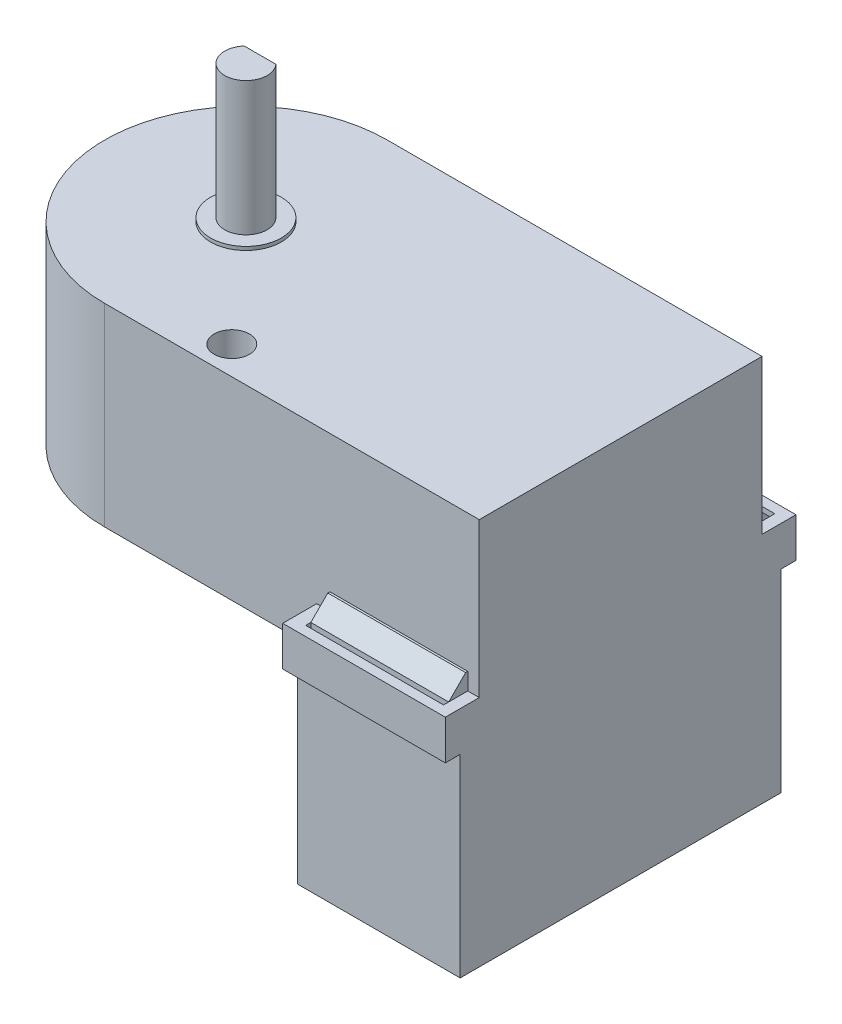
SolidWorks part; units mm, degrees
ref_plane "Спереди" through (0, 0, 0) normal (0, 0, 1) x (1, 0, 0)
ref_plane "Сверху" through (0, 0, 0) normal (0, 1, 0) x (1, 0, 0)
ref_plane "Справа" through (0, 0, 0) normal (1, 0, 0) x (0, 0, -1)
sketch "Эскиз1" plane through (0, 0, 0) normal (0, 1, 0) x (1, 0, 0)
  line L1 (-13.25, 10) -> (13.25, 10)
  line L3 (-13.25, -10) -> (13.25, -10)
  line L4 (13.25, 10) -> (13.25, -10)
  arc A0 (-13.25, -10) -> (-13.25, 10) centre (-13.25, 0) cw
extrude "Вытянуть1" add sketch "Эскиз1" along normal blind 13.7
sketch "Эскиз2" plane through (0, 13.7, 0) normal (0, 1, 0) x (1, 0, 0)
  line L0 (-13.25, 0) -> (-6.946, 0) construction
  line L1 (-14.368, 1) -> (-12.132, 1)
  arc A0 (-14.368, 1) -> (-12.132, 1) centre (-13.25, 0) ccw
  dimension "D1" = 1
extrude "Вытянуть2" add sketch "Эскиз2" along normal blind 9.7
sketch "Эскиз3" plane through (0, 0, 0) normal (0, -1, 0) x (1, 0, 0)
  line L1 (7.5, 14.2075) -> (7.5, -15.8701) construction
  line L2 (13.25, 10) -> (13.25, -10) construction
  line L3 (13.25, 0) -> (18.7862, 0) construction
  line L5 (1.75, -11.35) -> (13.25, -11.35)
  line L6 (1.75, -11.35) -> (1.75, 11.35)
  line L7 (1.75, 11.35) -> (13.25, 11.35)
  line L8 (13.25, -11.35) -> (13.25, 11.35)
  line L9 (1.75, -11.35) -> (13.25, 11.35) construction
  line L10 (1.75, 11.35) -> (13.25, -11.35) construction
  point P6 (7.5, 0)
  dimension "D1" = 5.75
extrude "Вытянуть3" add sketch "Эскиз3" along normal blind 13.7
sketch "Эскиз4" plane through (0, 0, -10) normal (0, 0, -1) x (-1, 0, 0)
  line L1 (-13.25, 0) -> (-1.75, 0)
  line L2 (-13.25, 0) -> (-13.25, 2.8)
  line L3 (-13.25, 2.8) -> (-1.75, 2.8)
  line L4 (-1.75, 0) -> (-1.75, 2.8)
extrude "Вытянуть4" add sketch "Эскиз4" along normal blind 2.4
sketch "Эскиз5" plane through (0, 0, 10) normal (0, 0, 1) x (1, 0, 0)
  line L1 (13.25, 0) -> (1.75, 0)
  line L2 (13.25, 0) -> (13.25, 2.8)
  line L3 (13.25, 2.8) -> (1.75, 2.8)
  line L4 (1.75, 0) -> (1.75, 2.8)
extrude "Вытянуть5" add sketch "Эскиз5" along normal blind 2.4
sketch "Эскиз6" plane through (0, 2.8, 0) normal (0, 1, 0) x (1, 0, 0)
  line L0 (1.75, 10) -> (13.25, 10) construction
  line L1 (2.6894, 11.7136) -> (12.4382, 11.7136)
  line L2 (2.6894, 11.7136) -> (2.6894, 10)
  line L3 (2.6894, 10) -> (12.4382, 10)
  line L4 (12.4382, 11.7136) -> (12.4382, 10)
  line L5 (13.25, 0) -> (19.5797, 0) construction
  line L7 (12.4382, -11.7136) -> (12.4382, -10)
  line L8 (2.6894, -10) -> (12.4382, -10)
  line L9 (2.6894, -11.7136) -> (2.6894, -10)
  line L10 (2.6894, -11.7136) -> (12.4382, -11.7136)
extrude "Вытянуть7" cut sketch "Эскиз6" against normal up to surface (2.8 mm away) up to face at (7.5, 0, -11.875)
sketch "Эскиз7" plane through (0, 0, 0) normal (0, 1, 0) x (1, 0, 0)
  line L0 (12.4382, 10) -> (12.4382, 11.7136) construction
  line L1 (2.6894, 11.35) -> (12.4382, 11.35)
  line L2 (2.6894, 11.35) -> (2.6894, 10)
  line L3 (2.6894, 10) -> (12.4382, 10)
  line L4 (12.4382, 11.35) -> (12.4382, 10)
  line L5 (12.4382, 11.35) -> (12.4382, 10) construction
  line L6 (0, 0) -> (18.4843, 0) construction
  line L7 (12.4382, -11.35) -> (12.4382, -10)
  line L8 (2.6894, -10) -> (12.4382, -10)
  line L9 (2.6894, -11.35) -> (2.6894, -10)
  line L10 (2.6894, -11.35) -> (12.4382, -11.35)
extrude "Вытянуть8" add sketch "Эскиз7" along normal blind 4
chamfer "Фаска1" distance 1.2 angle 45 2 edges at (7.5638, 4, -11.35) (7.5638, 4, 11.35)
sketch "Эскиз8" plane through (0, 13.7, 0) normal (0, 1, 0) x (1, 0, 0)
  circle A0 centre (-13.25, 0) radius 2.5
extrude "Вытянуть9" add sketch "Эскиз8" along normal blind 0.25
sketch "Эскиз9" plane through (0, 13.7, 0) normal (0, 1, 0) x (1, 0, 0)
  line L0 (13.25, -10) -> (13.25, 10) construction
  line L2 (-13.25, -10) -> (13.25, -10) construction
  circle A0 centre (-6.25, -8) radius 1.25
  dimension "D1" = 19.5
  dimension "D2" = 2
extrude "Вытянуть10" cut sketch "Эскиз9" against normal through all
